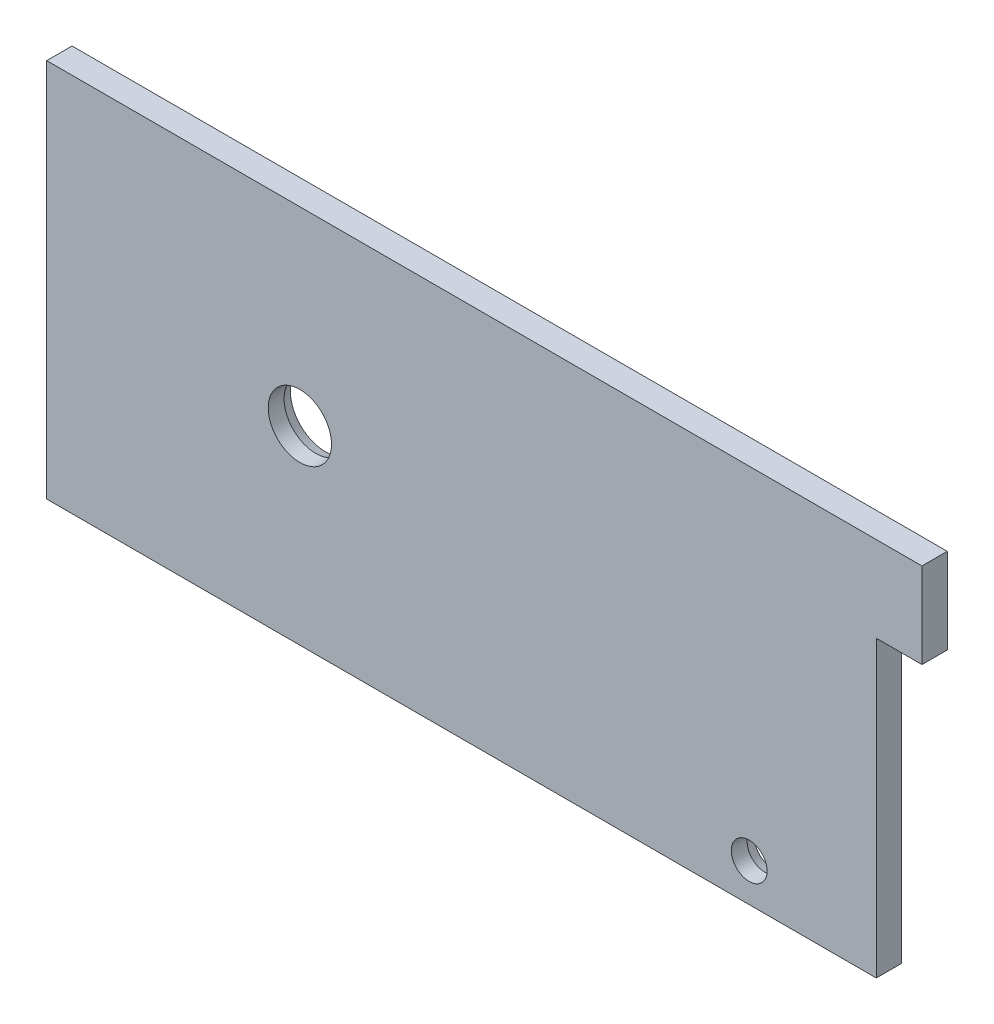
SolidWorks part; units mm, degrees
ref_plane "Front Plane" through (0, 0, 0) normal (0, 0, 1) x (1, 0, 0)
ref_plane "Top Plane" through (0, 0, 0) normal (0, 1, 0) x (1, 0, 0)
ref_plane "Right Plane" through (0, 0, 0) normal (1, 0, 0) x (0, 0, -1)
sketch "Sketch1" plane through (0, 0, 0) normal (0, 0, 1) x (1, 0, 0)
  line L1 (-81, -30) -> (50.0797, -30)
  line L6 (57.3, 16.5) -> (50.0797, 16.5)
  line L11 (57.3, 16.5) -> (57.3, 30)
  line L13 (50.0797, 16.5) -> (50.0797, -30)
  line L18 (57.3, 30) -> (-81, 30)
  line L19 (-81, 30) -> (-81, -30)
  circle A4 centre (-41, 0) radius 5
  circle A5 centre (30, -24) radius 2.83
  point P4 (-81, 0)
  dimension "D5" = 10
  dimension "D9" = 5.66
  dimension "D8" = 13.5
  dimension "D10" = 60
  dimension "D2" = 138.3
  dimension "D3" = 40
  dimension "D4" = 71
  dimension "D6" = 24
extrude "Boss-Extrude1" add sketch "Sketch1" along normal mid plane 4
chamfer "Chamfer1" distance 1.5 distance2 0.5 2 edges at (32.83, -24, -2) (-36, 0, -2) first distance on face at (32.83, -24, 2) first distance on face at (-36, 0, 2)
equation "\"back_boost\"= 7"
equation "\"D3@Sketch1\"=\"back_boost\"+33.00mm"
equation "\"D2@Sketch1\"=\"back_boost\"+131.30mm"
